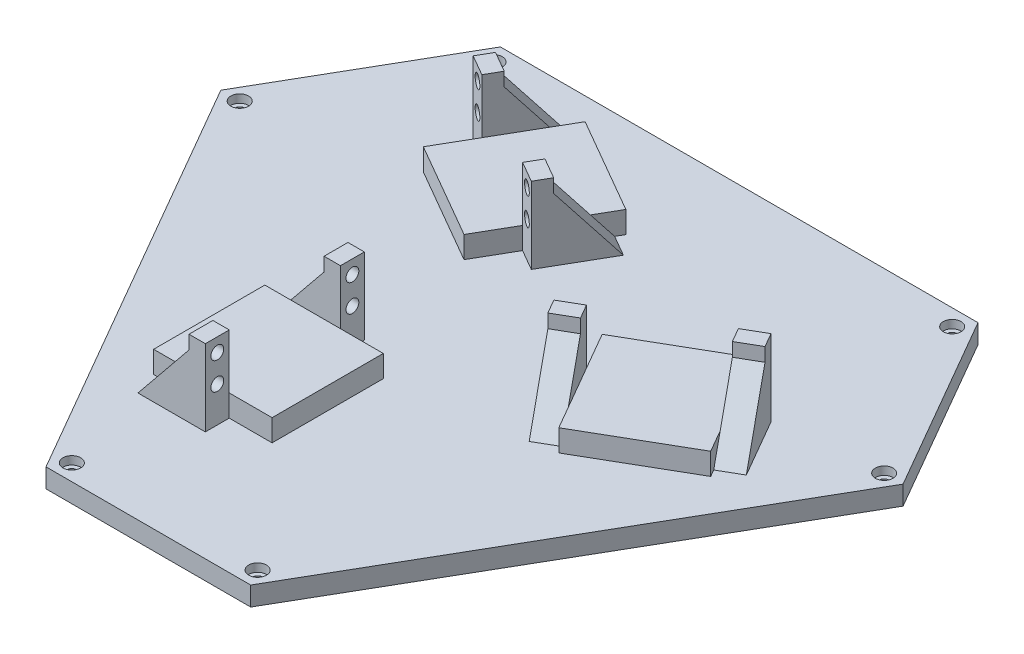
SolidWorks part; units mm, degrees
ref_plane "Front Plane" through (0, 0, 0) normal (0, 0, 1) x (1, 0, 0)
ref_plane "Top Plane" through (0, 0, 0) normal (0, 1, 0) x (1, 0, 0)
ref_plane "Right Plane" through (0, 0, 0) normal (1, 0, 0) x (0, 0, -1)
sketch "Sketch1" plane through (0, 0, 0) normal (0, 1, 0) x (1, 0, 0)
  line L14 (-106.25, 184.0304) -> (81.25, 75.7772) construction
  line L15 (87.5, 216.5064) -> (-87.5, 216.5064)
  line L16 (-87.5, 216.5064) -> (-125, 151.5544)
  line L17 (-125, 151.5544) -> (-37.5, 0)
  line L18 (-37.5, 0) -> (37.5, 0)
  line L19 (37.5, 0) -> (125, 151.5544)
  line L20 (125, 151.5544) -> (87.5, 216.5064)
  line L21 (106.25, 184.0304) -> (-81.25, 75.7772) construction
  line L22 (0, 216.5064) -> (0, 0) construction
  line L23 (87.5, 216.5064) -> (-37.5, 0) construction
  line L24 (-87.5, 216.5064) -> (37.5, 0) construction
  line L25 (125, 151.5544) -> (-125, 151.5544) construction
  point P1 (0, 216.5064)
  point P8 (0, 122.6869)
  dimension "D1" = 175
  dimension "D2" = 75
  dimension "D3" = 120
extrude "Boss-Extrude1" add sketch "Sketch1" along normal blind 7
sketch "Sketch2" plane through (0, 7, 0) normal (0, 1, 0) x (1, 0, 0)
  line L4 (84.8319, 123.0662) -> (73.4819, 142.725) construction
  line L5 (87.3319, 118.7361) -> (52.0414, 98.3611) construction
  line L6 (-40.2444, 200.294) -> (-4.9539, 179.919) construction
  line L8 (-40.2444, 200.294) -> (-42.7444, 195.9639) construction
  line L9 (79.4358, 146.1625) -> (32.2374, 118.9125) construction
  line L10 (-47.0875, 49.0307) -> (-42.0875, 49.0307) construction
  line L12 (-47.0875, 49.0307) -> (-47.0875, 89.7807) construction
  line L13 (-19.3875, 42.1557) -> (-19.3875, 96.6557) construction
  line L14 (-3.6875, 89.7807) -> (-3.6875, 49.0307) construction
  line L15 (-60.0483, 179.7426) -> (-12.8499, 152.4926) construction
  line L16 (-26.6539, 142.3335) -> (-4.9539, 179.919)
  line L17 (-26.6539, 142.3335) -> (-61.9444, 162.7085)
  line L18 (-4.9539, 179.919) -> (-40.2444, 200.294)
  line L19 (-61.9444, 162.7085) -> (-40.2444, 200.294)
  line L21 (-3.6875, 89.7807) -> (-47.0875, 89.7807)
  line L22 (-3.6875, 89.7807) -> (-3.6875, 49.0307)
  line L23 (-47.0875, 89.7807) -> (-47.0875, 49.0307)
  line L24 (-3.6875, 49.0307) -> (-47.0875, 49.0307)
  line L26 (30.3414, 135.9466) -> (52.0414, 98.3611)
  line L27 (30.3414, 135.9466) -> (65.6319, 156.3216)
  line L28 (52.0414, 98.3611) -> (87.3319, 118.7361)
  line L29 (65.6319, 156.3216) -> (87.3319, 118.7361)
  line L31 (-54.0944, 176.3051) -> (-61.6721, 180.6801)
  line L32 (-54.0944, 176.3051) -> (-51.0944, 181.5013)
  line L33 (-61.6721, 180.6801) -> (-58.6721, 185.8763)
  line L34 (-51.0944, 181.5013) -> (-58.6721, 185.8763)
  line L35 (-18.8039, 155.9301) -> (-11.2261, 151.5551)
  line L36 (-18.8039, 155.9301) -> (-15.8039, 161.1263)
  line L37 (-11.2261, 151.5551) -> (-8.2261, 156.7513)
  line L38 (-15.8039, 161.1263) -> (-8.2261, 156.7513)
  line L39 (81.0596, 147.1) -> (73.4819, 142.725)
  line L40 (81.0596, 147.1) -> (84.0596, 141.9038)
  line L41 (73.4819, 142.725) -> (76.4819, 137.5288)
  line L42 (84.0596, 141.9038) -> (76.4819, 137.5288)
  line L43 (30.6136, 117.975) -> (38.1914, 122.35)
  line L44 (30.6136, 117.975) -> (33.6136, 112.7788)
  line L45 (38.1914, 122.35) -> (41.1914, 117.1538)
  line L46 (33.6136, 112.7788) -> (41.1914, 117.1538)
  line L47 (-19.3875, 98.5307) -> (-19.3875, 89.7807)
  line L48 (-19.3875, 98.5307) -> (-25.3875, 98.5307)
  line L49 (-19.3875, 89.7807) -> (-25.3875, 89.7807)
  line L50 (-25.3875, 98.5307) -> (-25.3875, 89.7807)
  line L51 (-19.3875, 49.0307) -> (-19.3875, 40.2807)
  line L52 (-19.3875, 49.0307) -> (-25.3875, 49.0307)
  line L53 (-19.3875, 40.2807) -> (-25.3875, 40.2807)
  line L54 (-25.3875, 49.0307) -> (-25.3875, 40.2807)
  dimension "D1" = 6
  dimension "D2" = 8.75
extrude "Boss-Extrude2" add sketch "Sketch2" along normal blind 8 contours L19 L17 L16 L18 | L24 L22 L21 L23 | L29 L27 L26 L28 region at (-33.4491, 7, -171.3138) region at (-25.3875, 7, -69.4057) region at (58.8366, 7, -127.3413)
extrude "Boss-Extrude3" add sketch "Sketch2<3>" along normal blind 28 contours L19 L34 L33 L31 | L38 L16 L35 L37 | L48 L50 L21 L47 | L24 L54 L53 L51 | L44 L46 L26 L43 | L42 L40 L39 L29 region at (-13.515, 7, -156.3407) region at (-56.3833, 7, -181.0907) region at (-22.3875, 7, -94.1557) region at (-22.3875, 7, -44.6557) region at (35.9025, 7, -117.5644) region at (78.7708, 7, -142.3144)
sketch "Sketch2<3>" plane through (0, 7, 0) normal (0, 1, 0) x (1, 0, 0) same geometry as "Sketch2"
sketch "Sketch3" plane through (-43.4313, 0, -75.2251) normal (-0.5, 0, -0.866) x (-0.866, 0, 0.5)
  circle A0 centre (-139.3747, 20) radius 2.35
  circle A1 centre (-139.3747, 30) radius 2.35
  circle A2 centre (-89.8747, 30) radius 2.35
  circle A3 centre (-89.8747, 20) radius 2.35
  arc A4 (-87.4247, 20.7925) -> (-87.4247, 19.2075) centre (-89.8747, 20) ccw construction
  dimension "D1" = 4.7
extrude "Cut-Extrude1" cut sketch "Sketch3" against normal blind 4
sketch "Sketch4" plane through (62.8187, 0, -108.8053) normal (-0.5, 0, 0.866) x (0.866, 0, 0.5)
  circle A0 centre (-139.3747, 30) radius 2.35
  circle A1 centre (-89.8747, 20) radius 2.35
  circle A2 centre (-89.8747, 30) radius 2.35
  circle A3 centre (-139.3747, 20) radius 2.35
  dimension "D1" = 4.7
extrude "Cut-Extrude2" cut sketch "Sketch4" against normal blind 4
sketch "Sketch6" plane through (-19.3875, 0, 0) normal (1, 0, 0) x (0, 0, -1)
  circle A0 centre (44.6557, 30) radius 2.35
  circle A1 centre (94.1557, 20) radius 2.35
  circle A2 centre (94.1557, 30) radius 2.35
  circle A3 centre (44.6557, 20) radius 2.35
  dimension "D1" = 4.7
extrude "Cut-Extrude6" cut sketch "Sketch6" against normal blind 4
hole_wizard "CBORE for M3 SHCS1" positions "Sketch8" profile "Sketch9" counterbore size "M3" standard "ANSI Metric" end condition up to next
sketch "Sketch8" plane through (0, 7, 0) normal (0, 1, 0) x (1, 0, 0)
  line L23 (118.0718, 151.5544) -> (84.0359, 210.5064)
  line L24 (84.0359, 210.5064) -> (-84.0359, 210.5064)
  line L25 (-84.0359, 210.5064) -> (-118.0718, 151.5544)
  line L26 (-118.0718, 151.5544) -> (-34.0359, 6)
  line L27 (-34.0359, 6) -> (34.0359, 6)
  line L28 (34.0359, 6) -> (118.0718, 151.5544)
  line L29 (118.0718, 151.5544) -> (84.0359, 210.5064) construction
  line L30 (84.0359, 210.5064) -> (-84.0359, 210.5064) construction
  line L31 (-84.0359, 210.5064) -> (-118.0718, 151.5544) construction
  line L32 (-118.0718, 151.5544) -> (-34.0359, 6) construction
  line L33 (-34.0359, 6) -> (34.0359, 6) construction
  line L34 (34.0359, 6) -> (118.0718, 151.5544) construction
  point P0 (-84.0359, 210.5064)
  point P2 (84.0359, 210.5064)
  point P4 (118.0718, 151.5544)
  point P6 (34.0359, 6)
  point P8 (-34.0359, 6)
  point P10 (-118.0718, 151.5544)
  dimension "D1" = 6
sketch "Sketch9" plane through (-84.0359, 7, -210.5064) normal (1, 0, 0) x (0, 0, 1)
  line L0 (0, 0) -> (0, 7)
  line L1 (0, 7) -> (1.7, 7)
  line L3 (1.7, 7) -> (1.7, 3)
  line L4 (1.7, 3) -> (3.25, 3)
  line L5 (3.25, 3) -> (3.25, 0)
  line L7 (3.25, 0) -> (0, 0)
  line L11 (0, -6.35) -> (0, 107.95) construction
  dimension "Thru Hole Dia." = 3.4
  dimension "Thru Hole Depth" = 7
  dimension "C'Bore Dia." = 6.5
  dimension "C'Bore Depth" = 3
ref_plane "Plane2" through (0, 0, -44.6557) normal (0, 0, 1) x (1, 0, 0)
sketch "Sketch12" plane through (0, 0, -44.6557) normal (0, 0, 1) x (1, 0, 0)
  line L0 (-25.3875, 30) -> (-44.0875, 7)
  line L1 (-25.3875, 35) -> (-25.3875, 7) construction
  line L2 (-25.3875, 7) -> (-47.0875, 7) construction
  line L4 (-19.3875, 35) -> (-25.3875, 35) construction
  dimension "D1" = 5
  dimension "D2" = 3
rib "Rib1" sketch "Sketch12" sketch "Sketch12" thickness 8.75 extrusion direction parallel to sketch draft on no parameters "D1"=8.75
ref_plane "Plane3" through (0, 0, -94.1557) normal (0, 0, 1) x (1, 0, 0)
sketch "Sketch13" plane through (0, 0, -94.1557) normal (0, 0, 1) x (1, 0, 0)
  line L0 (-25.3875, 30) -> (-44.0875, 7)
  line L1 (37.5, 7) -> (125, 7) construction
  line L2 (-25.3875, 15) -> (-25.3875, 7) construction
  dimension "D1" = 5
  dimension "D2" = 3
rib "Rib4" sketch "Sketch13" sketch "Sketch13" thickness 8.75 extrusion direction parallel to sketch draft on no parameters "D1"=8.75
ref_plane "Plane4" through (-120.702, 0, -69.6873) normal (-0.866, 0, -0.5) x (-0.5, 0, 0.866)
sketch "Sketch14" plane through (-120.702, 0, -69.6873) normal (-0.866, 0, -0.5) x (-0.5, 0, 0.866)
  line L0 (-131.6375, 30) -> (-150.3375, 7)
  line L1 (-131.6375, 35) -> (-131.6375, 7) construction
  line L2 (-131.6375, 7) -> (-153.3375, 7) construction
  line L3 (-153.3375, 15) -> (-153.3375, 7) construction
  dimension "D1" = 5
  dimension "D2" = 3
rib "Rib5" sketch "Sketch14" sketch "Sketch14" thickness 8.75 extrusion direction parallel to sketch draft on no parameters "D1"=8.75
ref_plane "Plane5" through (-77.8338, 0, -44.9373) normal (-0.866, 0, -0.5) x (-0.5, 0, 0.866)
sketch "Sketch15" plane through (-77.8338, 0, -44.9373) normal (-0.866, 0, -0.5) x (-0.5, 0, 0.866)
  line L0 (-131.6375, 30) -> (-150.3375, 7)
  line L1 (-131.6375, 35) -> (-131.6375, 30) construction
  line L2 (-150.3375, 7) -> (-153.3375, 7) construction
  line L3 (-125.6375, 35) -> (-131.6375, 35) construction
  dimension "D1" = 5
  dimension "D2" = 3
rib "Rib6" sketch "Sketch15" sketch "Sketch15" thickness 8.75 extrusion direction parallel to sketch draft on no parameters "D1"=8.75
ref_plane "Plane6" through (120.702, 0, -69.6873) normal (0.866, 0, -0.5) x (-0.5, 0, -0.866)
sketch "Sketch16" plane through (120.702, 0, -69.6873) normal (0.866, 0, -0.5) x (-0.5, 0, -0.866)
  line L0 (80.8625, 30) -> (62.1625, 7)
  line L1 (80.8625, 35) -> (80.8625, 7) construction
  line L2 (80.8625, 7) -> (59.1625, 7) construction
  line L3 (86.8625, 35) -> (80.8625, 35) construction
  line L4 (59.1625, 15) -> (59.1625, 7) construction
  dimension "D1" = 5
  dimension "D2" = 3
rib "Rib7" sketch "Sketch16" sketch "Sketch16" thickness 8.75 extrusion direction parallel to sketch draft on no parameters "D1"=8.75
ref_plane "Plane7" through (77.8338, 0, -44.9373) normal (0.866, 0, -0.5) x (-0.5, 0, -0.866)
sketch "Sketch17" plane through (77.8338, 0, -44.9373) normal (0.866, 0, -0.5) x (-0.5, 0, -0.866)
  line L0 (80.8625, 30) -> (62.1625, 7)
  line L1 (80.8625, 35) -> (80.8625, 30) construction
  line L2 (-18.75, 7) -> (68.75, 7) construction
  line L3 (86.8625, 35) -> (80.8625, 35) construction
  line L4 (59.1625, 15) -> (59.1625, 7) construction
  dimension "D1" = 5
  dimension "D2" = 3
rib "Rib8" sketch "Sketch17" sketch "Sketch17" thickness 8.75 extrusion direction parallel to sketch draft on no parameters "D1"=8.75
